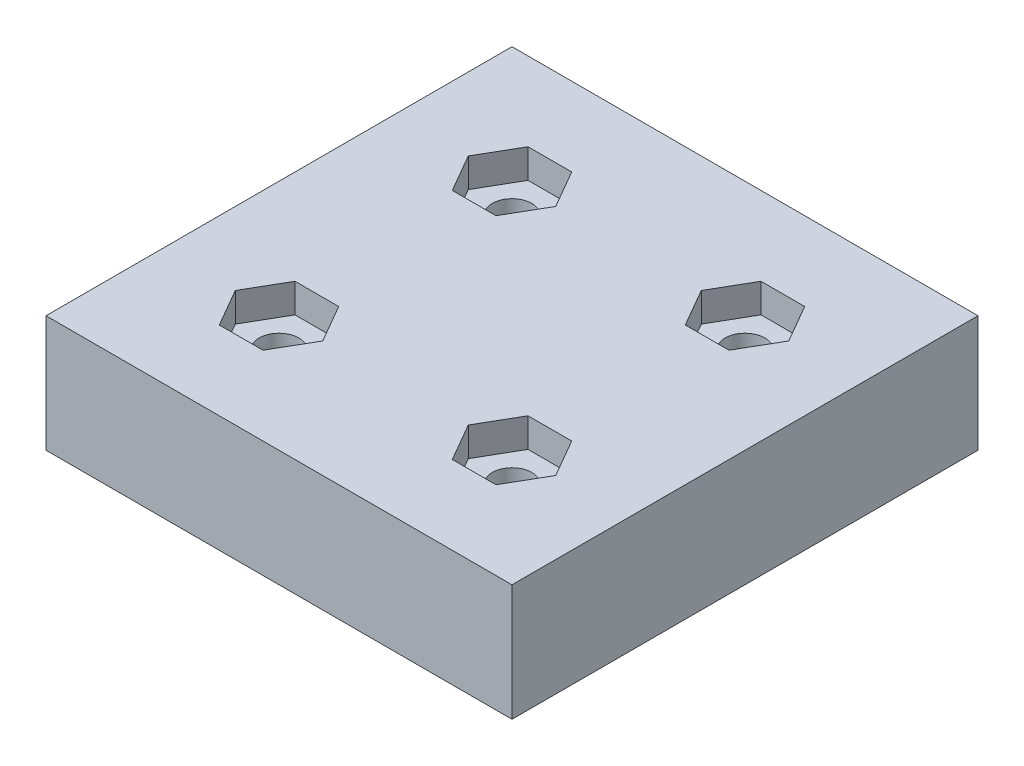
SolidWorks part; units mm, degrees
ref_plane "Front Plane" through (0, 0, 0) normal (0, 0, 1) x (1, 0, 0)
ref_plane "Top Plane" through (0, 0, 0) normal (0, 1, 0) x (1, 0, 0)
ref_plane "Right Plane" through (0, 0, 0) normal (1, 0, 0) x (0, 0, -1)
sketch "Sketch1" plane through (0, 0, 0) normal (0, 1, 0) x (1, 0, 0)
  line L1 (0, 0) -> (40, 0)
  line L2 (0, 0) -> (0, 40)
  line L3 (0, 40) -> (40, 40)
  line L4 (40, 0) -> (40, 40)
  circle A0 centre (10, 30) radius 1.7
  circle A1 centre (30, 30) radius 1.7
  circle A2 centre (30, 10) radius 1.7
  circle A3 centre (10, 10) radius 1.7
  dimension "D11" = 3.4
  dimension "D12" = 3.4
  dimension "D13" = 3.4
  dimension "D14" = 3.4
  dimension "D1" = 40
  dimension "D2" = 40
  dimension "D3" = 10
  dimension "D4" = 10
  dimension "D5" = 10
  dimension "D6" = 10
  dimension "D7" = 10
  dimension "D8" = 10
  dimension "D9" = 10
  dimension "D10" = 10
extrude "Boss-Extrude1" add sketch "Sketch1" along normal blind 10
sketch "Sketch2" plane through (0, 10, 0) normal (0, 1, 0) x (1, 0, 0)
  line L0 (10, 10) -> (30, 10) construction
  line L1 (30, 10) -> (30, 30) construction
  line L2 (30, 30) -> (10, 30) construction
  line L3 (10, 30) -> (10, 10) construction
  line L5 (13.7528, 10) -> (11.8764, 13.25)
  line L6 (11.8764, 13.25) -> (8.1236, 13.25)
  line L7 (8.1236, 13.25) -> (6.2472, 10)
  line L8 (6.2472, 10) -> (8.1236, 6.75)
  line L9 (8.1236, 6.75) -> (11.8764, 6.75)
  line L10 (11.8764, 6.75) -> (13.7528, 10)
  line L11 (26.2472, 10) -> (28.1236, 6.75)
  line L12 (28.1236, 6.75) -> (31.8764, 6.75)
  line L13 (31.8764, 6.75) -> (33.7528, 10)
  line L14 (33.7528, 10) -> (31.8764, 13.25)
  line L15 (31.8764, 13.25) -> (28.1236, 13.25)
  line L16 (28.1236, 13.25) -> (26.2472, 10)
  line L17 (26.2472, 30) -> (28.1236, 26.75)
  line L18 (28.1236, 26.75) -> (31.8764, 26.75)
  line L19 (31.8764, 26.75) -> (33.7528, 30)
  line L20 (33.7528, 30) -> (31.8764, 33.25)
  line L21 (31.8764, 33.25) -> (28.1236, 33.25)
  line L22 (28.1236, 33.25) -> (26.2472, 30)
  line L23 (13.7528, 30) -> (11.8764, 33.25)
  line L24 (11.8764, 33.25) -> (8.1236, 33.25)
  line L25 (8.1236, 33.25) -> (6.2472, 30)
  line L26 (6.2472, 30) -> (8.1236, 26.75)
  line L27 (8.1236, 26.75) -> (11.8764, 26.75)
  line L28 (11.8764, 26.75) -> (13.7528, 30)
  circle A0 centre (10, 10) radius 3.25 construction
  circle A1 centre (30, 10) radius 3.25 construction
  circle A2 centre (30, 30) radius 3.25 construction
  circle A3 centre (10, 30) radius 3.25 construction
  dimension "D1" = 6.5
  dimension "D2" = 6.5
  dimension "D3" = 6.5
  dimension "D4" = 6.5
extrude "Cut-Extrude1" cut sketch "Sketch2" against normal blind 2.5
equation "\"hSpacing\"=10"
equation "\"D3@Sketch1\"=\"hSpacing\""
equation "\"D5@Sketch1\"=\"hSpacing\""
equation "\"D6@Sketch1\"=\"hSpacing\""
equation "\"D4@Sketch1\"=\"hSpacing\""
equation "\"D7@Sketch1\"=\"hSpacing\""
equation "\"D8@Sketch1\"=\"hSpacing\""
equation "\"D9@Sketch1\"=\"hSpacing\""
equation "\"D10@Sketch1\"=\"hSpacing\""
equation "\"hDiam\"=3.4"
equation "\"D11@Sketch1\"=\"hDiam\""
equation "\"D12@Sketch1\"=\"hDiam\""
equation "\"D13@Sketch1\"=\"hDiam\""
equation "\"D14@Sketch1\"=\"hDiam\""
equation "\"nutFlat\"=6.5"
equation "\"D1@Sketch2\"=\"nutFlat\""
equation "\"D2@Sketch2\"=\"nutFlat\""
equation "\"D3@Sketch2\"=\"nutFlat\""
equation "\"D4@Sketch2\"=\"nutFlat\""
